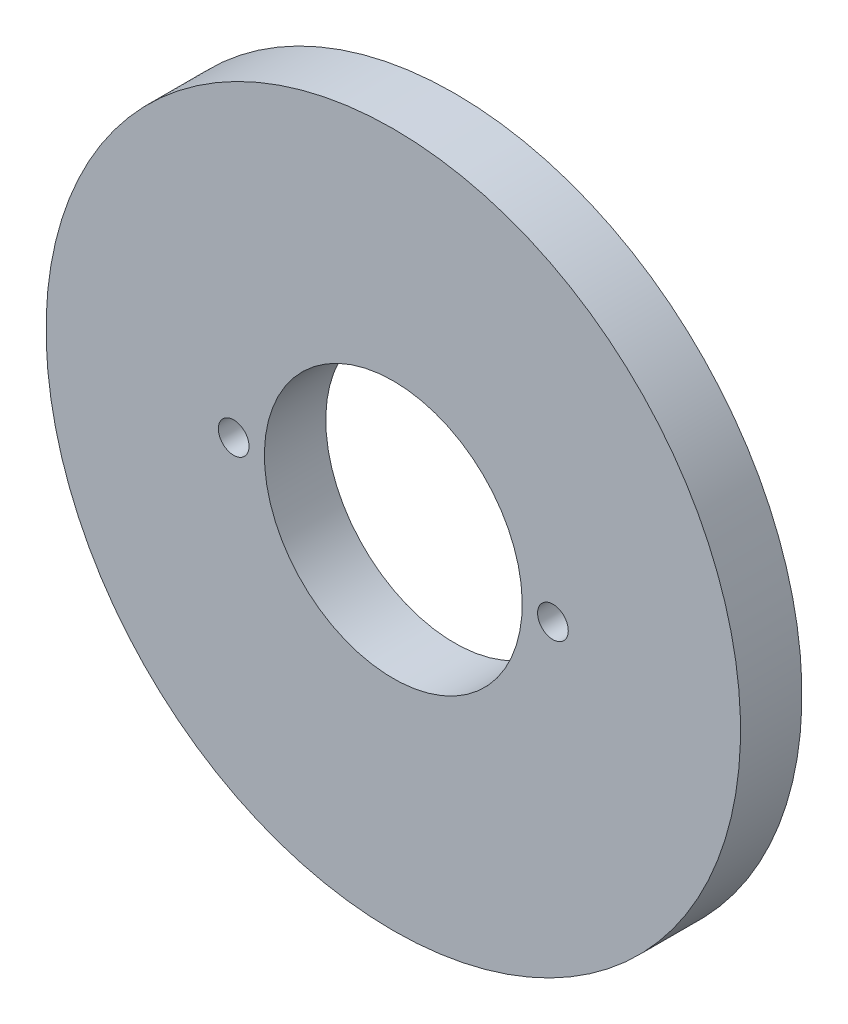
SolidWorks part; units mm, degrees
ref_plane "Front Plane" through (0, 0, 0) normal (0, 0, 1) x (1, 0, 0)
ref_plane "Top Plane" through (0, 0, 0) normal (0, 1, 0) x (1, 0, 0)
ref_plane "Right Plane" through (0, 0, 0) normal (1, 0, 0) x (0, 0, -1)
sketch "Sketch1" plane through (0, 0, 0) normal (1, 0, 0) x (0, 0, -1)
  line L0 (0, 13.335) -> (0, 10.5156)
  line L1 (0, 10.5156) -> (9.525, 10.5156)
  line L2 (9.525, 10.5156) -> (9.525, 35.9156)
  line L3 (9.525, 35.9156) -> (15.875, 35.9156)
  line L4 (15.875, 35.9156) -> (15.875, 13.335)
  line L5 (15.875, 0) -> (0, 0) construction
  line L6 (0, 13.335) -> (15.875, 13.335)
  line L7 (0, 0) -> (0, 13.335) construction
  line L8 (15.875, 13.335) -> (15.875, 0) construction
  dimension "D1" = 10.5156
  dimension "D2" = 9.525
  dimension "D3" = 6.35
  dimension "D4" = 13.335
  dimension "D5" = 25.4
revolve "Revolve1" add sketch "Sketch1" angle 360 about L5 region at (0, 24.6253, -12.7)
sketch "Sketch2" plane through (0, 0, -15.875) normal (0, 0, -1) x (-1, 0, 0)
  line L4 (-4.7625, 17.4596) -> (-4.7625, 24.6702)
  line L5 (-4.7625, 24.6702) -> (-1.5875, 24.6702)
  line L6 (-1.5875, 24.6702) -> (-1.5875, 13.2402)
  line L7 (0, 0) -> (0, 24.419) construction
  line L8 (1.5875, 24.6702) -> (1.5875, 13.2402)
  line L9 (4.7625, 24.6702) -> (1.5875, 24.6702)
  line L10 (4.7625, 17.4596) -> (4.7625, 24.6702)
  circle A3 centre (0, 0) radius 13.335
  arc A4 (-4.7625, 17.4596) -> (4.7625, 17.4596) centre (0, 0) ccw
  circle A5 centre (0, 0) radius 13.335 construction
  dimension "D3" = 4.7625
  dimension "D1" = 3.175
  dimension "D2" = 3.175
  dimension "D4" = 11.43
sketch "Sketch3" plane through (0, 0, -15.875) normal (0, 0, -1) x (-1, 0, 0)
  circle A0 centre (16.51, 0) radius 1.7272 construction
  circle A1 centre (-16.51, 0) radius 1.7272 construction
  circle A2 centre (16.51, 0) radius 1.7272 construction
  circle A3 centre (-16.51, 0) radius 1.7272 construction
  circle A4 centre (16.51, 0) radius 1.5875
  circle A5 centre (-16.51, 0) radius 1.5875
  dimension "D1" = 3.175
extrude "Cut-Extrude1" cut sketch "Sketch3" against normal through all
